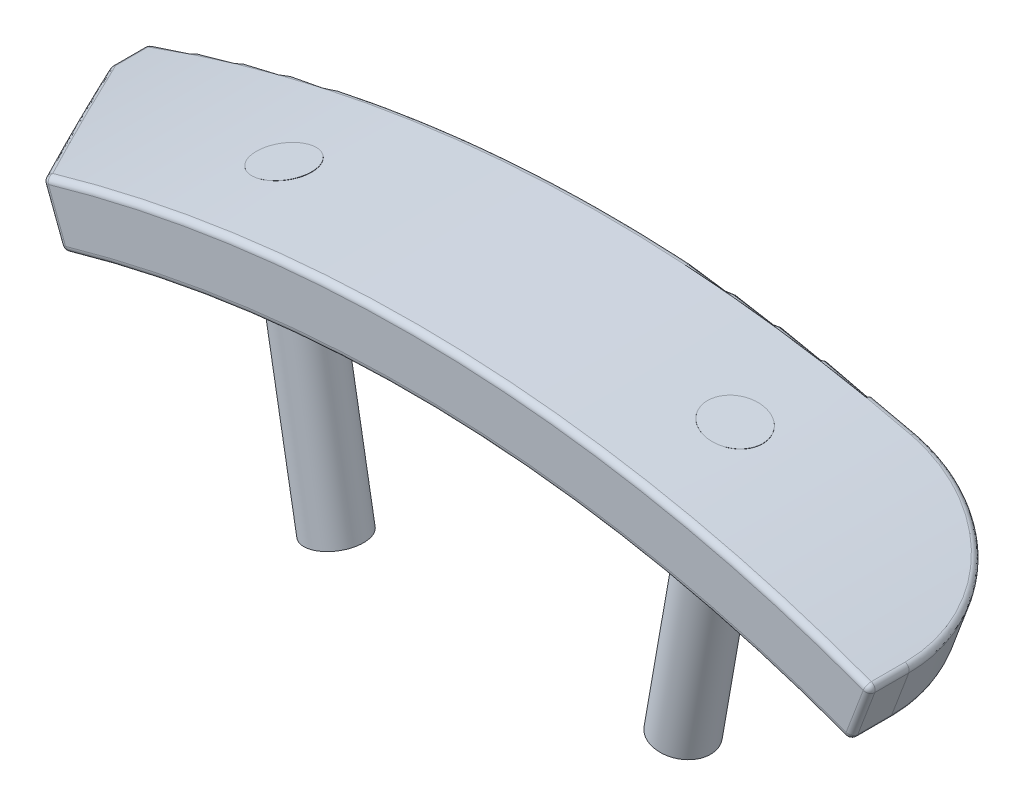
SolidWorks part; units mm, degrees
ref_plane "Front Plane" through (0, 0, 0) normal (0, 0, 1) x (1, 0, 0)
ref_plane "Top Plane" through (0, 0, 0) normal (0, 1, 0) x (1, 0, 0)
ref_plane "Right Plane" through (0, 0, 0) normal (1, 0, 0) x (0, 0, -1)
sketch "Sketch4" plane through (0, 0, 0) normal (0, 0, 1) x (1, 0, 0)
  line L0 (0, 62) -> (0, 65) construction
  line L1 (-22.0166, 57.9592) -> (-23.082, 60.7637)
  line L2 (22.0166, 57.9592) -> (23.082, 60.7637)
  arc A0 (22.0166, 57.9592) -> (-22.0166, 57.9592) centre (0, 0) ccw
  arc A1 (23.082, 60.7637) -> (-23.082, 60.7637) centre (0, 0) ccw
  dimension "D1" = 20.8
  dimension "D2" = 20.8
extrude "Boss-Extrude1" add sketch "Sketch4" along normal blind 10
fillet "Fillet2" radius 8 1 edges at (22.5493, 59.3614, 0)
chamfer "Chamfer1" distance 8 angle 32 1 edges at (-22.5493, 59.3614, 10) first distance on face at (-22.5493, 59.3614, 5)
fillet "Fillet3" radius 0.3 16 edges at (-4.0084, 61.8703, 0) (23.082, 60.7637, 9) (21.4352, 61.3639, 3.0031) (22.0166, 57.9592, 9) (19.1667, 58.963, 1.7386) (2.5015, 61.9495, 10) (22.5493, 59.3614, 10) (2.5013, 64.9519, 10) (-22.0166, 57.9592, 1) (-23.082, 60.7637, 1) (-4.0076, 64.8763, 0) (-19.6602, 58.8003, 6.0033) (-20.7265, 61.6069, 6.003) (-17.8061, 60.9523, 10) (-22.5493, 59.3614, 2) (-22.5493, 59.3614, 0)
ref_axis "Axis1" through (0, 0, 9.7) along (0, 0, -1)
ref_plane "Plane1" through (11.2871, 64.0125, 0) normal (0.1736, 0.9848, 0) x (0, 0, -1)
sketch "Sketch5" plane through (11.2871, 64.0125, 0) normal (0.1736, 0.9848, 0) x (0, 0, -1)
  line L0 (-9.7, 0) -> (0, 0) construction
  line L1 (0, -4.1722) -> (0, 32.8711) construction
  circle A0 centre (-5.0013, 0) radius 1.4
extrude "Boss-Extrude3" add sketch "Sketch5" against normal blind 15 contours A0
ref_plane "Plane2" through (-11.2871, 64.0125, 0) normal (-0.1736, 0.9848, 0) x (0, 0, -1)
sketch "Sketch6" plane through (-11.2871, 64.0125, 0) normal (-0.1736, 0.9848, 0) x (0, 0, -1)
  line L0 (-9.7, 0) -> (0, 0) construction
  line L1 (0, -26.0033) -> (0, 11.8288) construction
  circle A0 centre (-5, 0) radius 1.4
  dimension "D1" = 5
extrude "Boss-Extrude4" add sketch "Sketch6" against normal blind 15
ref_axis "Axis2" through (8.5993, 48.7688, 5.0013) along (0.1736, 0.9848, 0)
ref_axis "Axis3" through (-8.7475, 49.6098, 5) along (-0.1736, 0.9848, 0)
ref_point "Point2"
